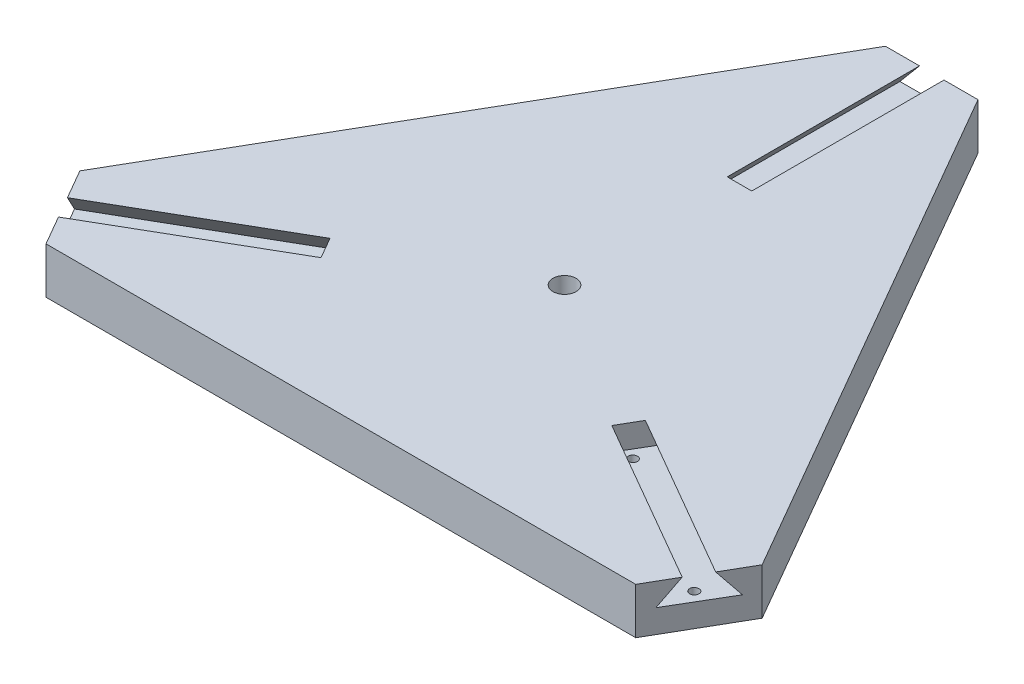
SolidWorks part; units mm, degrees
ref_plane "Plan de face" through (0, 0, 0) normal (0, 0, 1) x (1, 0, 0)
ref_plane "Plan de dessus" through (0, 0, 0) normal (0, 1, 0) x (1, 0, 0)
ref_plane "Plan de droite" through (0, 0, 0) normal (1, 0, 0) x (0, 0, -1)
sketch "Esquisse1" plane through (0, 0, 0) normal (0, 1, 0) x (1, 0, 0)
  line L29 (-10, 79.3725) -> (10, 79.3725)
  line L30 (73.7386, -31.026) -> (63.7386, -48.3465)
  line L31 (-63.7386, -48.3465) -> (-73.7386, -31.026)
  line L32 (-10, 79.3725) -> (-73.7386, -31.026)
  line L33 (-63.7386, -48.3465) -> (63.7386, -48.3465)
  line L34 (73.7386, -31.026) -> (10, 79.3725)
  circle A7 centre (0, 0) radius 2.5
  circle A8 centre (0, 0) radius 79.3725 construction
  point P17 (0, 0)
  dimension "D1" = 20
  dimension "D4" = 20
  dimension "D5" = 80
  dimension "D6" = 80
  dimension "D3" = 80
  dimension "D9" = 5
  dimension "D12" = 79.3725
  dimension "D2" = 20
  dimension "D7" = 60
  dimension "D8" = 60
  dimension "D10" = 80
  dimension "D11" = 80
extrude "Boss.-Extru.1" add sketch "Esquisse1" along normal mid plane 10
sketch "Esquisse2" plane through (0, 5, 0) normal (0, 1, 0) x (1, 0, 0)
  line L0 (-68.7386, -39.6863) -> (0, 0) construction
  line L1 (-73.7386, -31.026) -> (-63.7386, -48.3465) construction
  circle A0 centre (-66.3571, -38.3113) radius 1
  circle A1 centre (-34.9203, -20.1613) radius 1
  dimension "D1" = 2
  dimension "D4" = 2
  dimension "D2" = 2.75
  dimension "D3" = 39.05
extrude "Enlèv. mat.-Extru.1" cut sketch "Esquisse2" against normal through all
pattern_circular "Répétition circulaire1" count 3 over 360 about axis through (0, 5, 0) along (0, -1, 0) of "Enlèv. mat.-Extru.1" reverse direction yes
sketch "Esquisse3" plane through (68.7386, 0, 39.6863) normal (0.866, 0, 0.5) x (0.5, 0, -0.866)
  line L0 (2.65, 5) -> (6.8828, -0.0444)
  line L1 (-10, 5) -> (10, 5) construction
  line L3 (-6.8072, 0.0456) -> (-2.65, 5)
  line L4 (-2.65, 5) -> (2.65, 5)
  line L5 (-6.8072, 0.0456) -> (6.8828, -0.0444)
  point P6 (0, 5)
  dimension "D1" = 5.3
  dimension "D2" = 13.69
  dimension "D3" = 50
  dimension "D4" = 50
  dimension "D5" = 0.377
extrude "Enlèv. mat.-Extru.2" cut sketch "Esquisse3" against normal blind 41.553
pattern_circular "Répétition circulaire2" count 3 over 360 about axis through (0, 5, 0) along (0, -1, 0) of "Enlèv. mat.-Extru.2"
